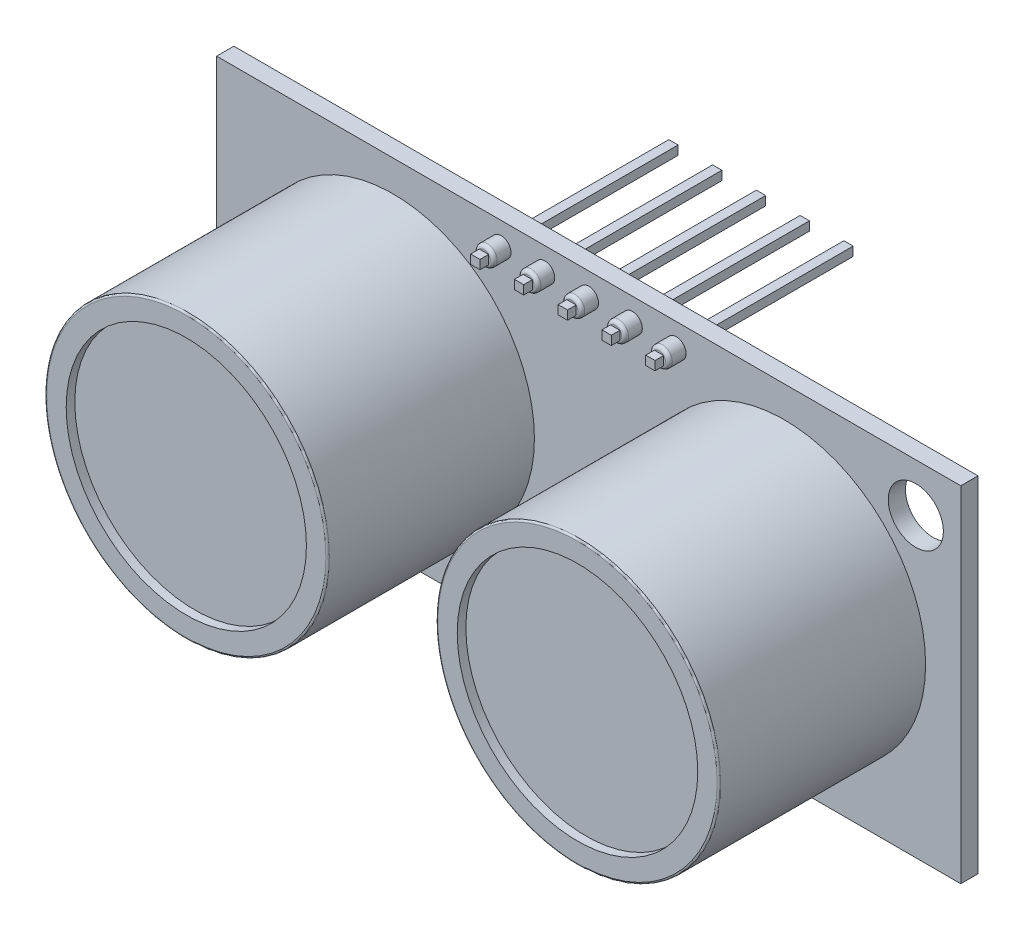
SolidWorks part; units mm, degrees
ref_plane "Front Plane" through (0, 0, 0) normal (0, 0, 1) x (1, 0, 0)
ref_plane "Top Plane" through (0, 0, 0) normal (0, 1, 0) x (1, 0, 0)
ref_plane "Right Plane" through (0, 0, 0) normal (1, 0, 0) x (0, 0, -1)
sketch "Sketch1" plane through (0, 0, 0) normal (0, 0, 1) x (1, 0, 0)
  line L0 (-38.8467, 18.9281) -> (4.3333, 18.9281) construction
  line L1 (-38.8467, 28.9281) -> (4.3333, 28.9281)
  line L2 (-38.8467, 28.9281) -> (-38.8467, 8.9281)
  line L3 (-38.8467, 8.9281) -> (4.3333, 8.9281)
  line L4 (4.3333, 28.9281) -> (4.3333, 8.9281)
  line L5 (1.7236, 26.1281) -> (-36.2369, 11.7281) construction
  circle A0 centre (1.7236, 26.1281) radius 1.6
  circle A1 centre (-36.2369, 11.7281) radius 1.5387
  point P10 (-17.2567, 18.9281)
  dimension "D3" = 3.2
  dimension "D1" = 43.18
  dimension "D2" = 20
  dimension "D5" = 40.6
  dimension "D6" = 2.8
extrude "Extrude1" add sketch "Sketch1" along normal blind 1
sketch "Sketch2" plane through (0, 0, 1) normal (0, 0, 1) x (1, 0, 0)
  line L0 (1.7236, 26.1281) -> (-36.2369, 11.7281) construction
  line L1 (-28.6067, 18.9281) -> (-5.9067, 18.9281) construction
  line L2 (-17.2567, 28.9281) -> (-17.2567, 8.9281) construction
  line L3 (4.3333, 28.9281) -> (-38.8467, 28.9281) construction
  line L4 (-38.8467, 8.9281) -> (4.3333, 8.9281) construction
  circle A0 centre (-28.6067, 18.9281) radius 8.2
  circle A1 centre (-5.9067, 18.9281) radius 8.2
  point P2 (-17.2567, 18.9281)
  dimension "D1" = 16.4
  dimension "D3" = 22.7
extrude "Extrude2" add sketch "Sketch2" along normal blind 12
sketch "Sketch3" plane through (0, 0, 13) normal (0, 0, 1) x (1, 0, 0)
  circle A0 centre (-28.6067, 18.9281) radius 6.9697
  circle A1 centre (-5.9067, 18.9281) radius 6.9784
extrude "Extrude3" cut sketch "Sketch3" against normal blind 0.5
fillet "Fillet1" radius 0.1 2 edges at (2.2933, 18.9281, 13) (-20.4067, 18.9281, 13)
sketch "Sketch6" plane through (0, 0, 1) normal (0, 0, 1) x (1, 0, 0)
  line L0 (-17.2567, 28.9281) -> (-17.2567, 8.9281) construction
  line L1 (4.3333, 28.9281) -> (-38.8467, 28.9281) construction
  line L2 (-38.8467, 8.9281) -> (4.3333, 8.9281) construction
  line L3 (-22.3367, 27.8537) -> (-22.3367, 27.332) construction
  line L7 (-22.6066, 27.8537) -> (-22.0668, 27.8537)
  line L11 (-22.6066, 27.8537) -> (-22.6066, 27.332)
  line L12 (-22.6066, 27.332) -> (-22.0668, 27.332)
  line L13 (-22.0668, 27.8537) -> (-22.0668, 27.332)
  point P6 (-22.3367, 27.332)
  point P7 (-22.3367, 27.8537)
  dimension "D1" = 5.08
extrude "Extrude6" add sketch "Sketch6" along normal blind 1.5 and the other way blind 10
sketch "Sketch9" plane through (0, 0, 1) normal (0, 0, 1) x (1, 0, 0)
  line L0 (-17.2567, 28.9281) -> (-17.2567, 20.2525) construction
  line L1 (4.3333, 28.9281) -> (-38.8467, 28.9281) construction
  circle B0 centre (-22.3367, 27.5929) radius 0.5705
  circle B1 centre (-12.1767, 27.5929) radius 0.5705
  circle B2 centre (-14.7167, 27.5929) radius 0.5705
  circle B3 centre (-17.2567, 27.5929) radius 0.5705
  circle B4 centre (-19.7967, 27.5929) radius 0.5705
  dimension "D1" = 5.08
sketch_block_instance "Block1-1"
sketch_block "Block1" parameters "D2"=1.141, "D1"=5
extrude "Extrude11" add sketch "Sketch9" along normal blind 1
fillet "Fillet2" radius 0.2 1 edges at (-21.7662, 27.5929, 2)
fillet "Fillet3" radius 0.2 4 edges at (-11.6062, 27.5929, 2) (-14.1462, 27.5929, 2) (-16.6862, 27.5929, 2) (-19.2262, 27.5929, 2)
pattern_linear "LPattern6" count 5 spacing 2.54 along (1, 0, 0) of "Extrude6"
sketch "Sketch34" plane through (0, 0, 1) normal (0, 0, 1) x (1, 0, 0)
  line L0 (-17.2567, 8.9281) -> (-17.2567, 28.9281) construction
  line L1 (-38.8467, 8.9281) -> (4.3333, 8.9281) construction
  line L2 (4.3333, 28.9281) -> (-38.8467, 28.9281) construction
  circle A0 centre (-17.2567, 12.4281) radius 3
  dimension "D1" = 6
  dimension "D2" = 3.5
extrude "Boss-Extrude1" add sketch "Sketch34" along normal blind 5
